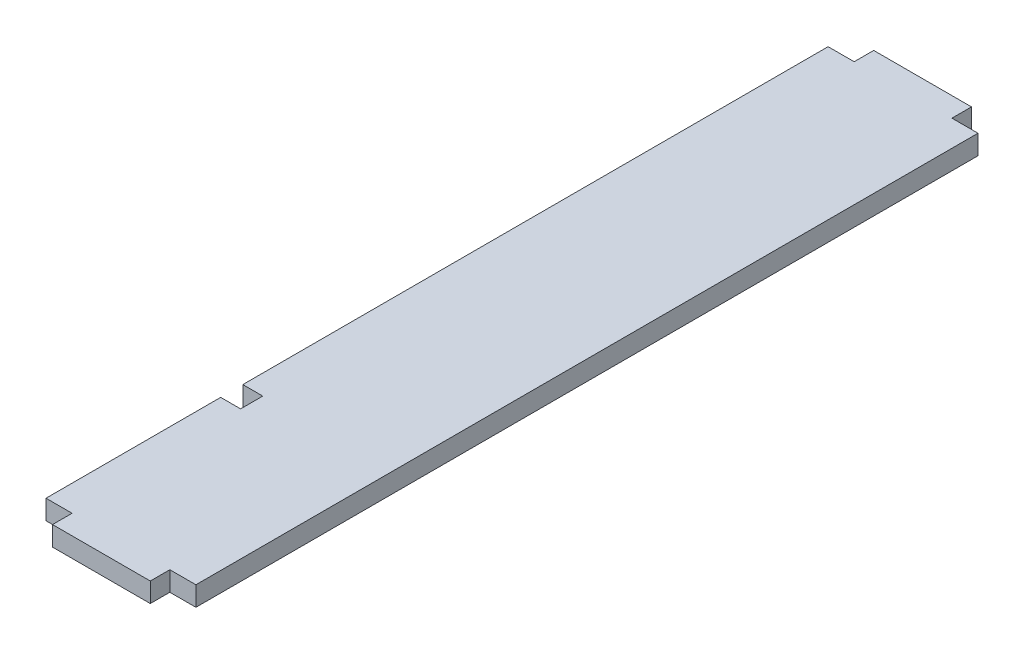
SolidWorks part; units mm, degrees
material "AISI 304"
ref_plane "Front Plane" through (0, 0, 0) normal (0, 0, 1) x (1, 0, 0)
ref_plane "Top Plane" through (0, 0, 0) normal (0, 1, 0) x (1, 0, 0)
ref_plane "Right Plane" through (0, 0, 0) normal (1, 0, 0) x (0, 0, -1)
sketch "Sketch1" plane through (0, 0, 0) normal (0, 1, 0) x (1, 0, 0)
  line L0 (3.75, 30) -> (5.75, 30)
  line L1 (-5.75, -30) -> (-3.75, -30)
  line L2 (-5.75, -30) -> (-5.75, -16.6)
  line L3 (-5.75, 30) -> (-3.75, 30)
  line L4 (5.75, -30) -> (5.75, 30)
  line L5 (-5.75, -30) -> (5.75, 30) construction
  line L6 (-5.75, 30) -> (5.75, -30) construction
  line L8 (3.75, 30) -> (3.75, 31.5)
  line L9 (3.75, 31.5) -> (-3.75, 31.5)
  line L10 (-3.75, 30) -> (-3.75, 31.5)
  line L12 (-3.75, -30) -> (-3.75, -31.5)
  line L13 (-3.75, -31.5) -> (3.75, -31.5)
  line L14 (3.75, -30) -> (3.75, -31.5)
  line L15 (3.75, -30) -> (5.75, -30)
  line L16 (-5.75, -14.9) -> (-5.75, 30)
  line L17 (-5.75, -14.9) -> (-4.2205, -14.9)
  line L19 (-5.75, -16.6) -> (-4.2205, -16.6)
  line L20 (-4.2205, -14.9) -> (-4.2205, -16.6)
  point P0 (0, 0)
  dimension "D1" = 7.5
  dimension "D2" = 2
  dimension "D3" = 2
  dimension "D4" = 1.5
  dimension "D5" = 2
  dimension "D6" = 2
  dimension "D7" = 1.5
  dimension "D8" = 60
  dimension "D12" = 1.5295
extrude "Boss-Extrude1" add sketch "Sketch1" along normal blind 1.5
